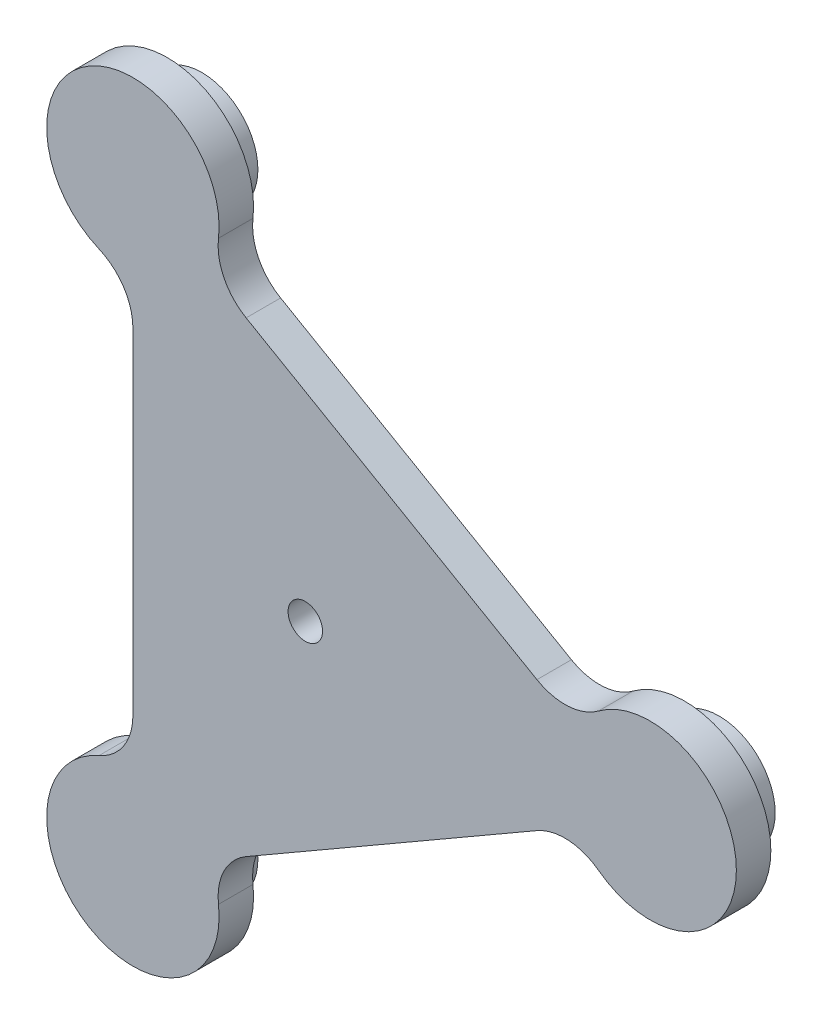
SolidWorks part; units mm, degrees
ref_plane "Front Plane" through (0, 0, 0) normal (0, 0, 1) x (1, 0, 0)
ref_plane "Top Plane" through (0, 0, 0) normal (0, 1, 0) x (1, 0, 0)
ref_plane "Right Plane" through (0, 0, 0) normal (1, 0, 0) x (0, 0, -1)
sketch "Sketch1" plane through (0, 0, 0) normal (0, 0, -1) x (1, 0, 0)
  line L0 (67.1651, 18.9572) -> (-17.1652, 67.6453)
  line L1 (-17.1652, -67.6453) -> (67.1652, -18.9572)
  line L6 (-50, 48.6881) -> (-50, -48.6881)
  arc A1 (-59.8485, -63.6241) -> (-25.1758, -83.6423) centre (-50, -86.6025) ccw
  circle A3 centre (-50, -86.6025) radius 16.25 construction
  arc A4 (-59.8485, -63.6241) -> (-50, -48.6881) centre (-66.25, -48.6881) ccw
  arc A5 (-25.1758, -83.6423) -> (-17.1652, -67.6453) centre (-9.0402, -81.7182) cw
  arc A6 (-25.1759, 83.6423) -> (-59.8485, 63.6241) centre (-50, 86.6025) ccw
  circle A7 centre (-50, 86.6025) radius 16.25 construction
  arc A8 (-25.1759, 83.6423) -> (-17.1652, 67.6453) centre (-9.0402, 81.7182) ccw
  arc A9 (-59.8485, 63.6241) -> (-50, 48.6881) centre (-66.25, 48.6881) cw
  arc A10 (85.0243, -20.0182) -> (85.0243, 20.0183) centre (100, 0) ccw
  circle A11 centre (100, 0) radius 16.25 construction
  arc A12 (85.0243, -20.0182) -> (67.1652, -18.9572) centre (75.2902, -33.0301) ccw
  arc A13 (85.0243, 20.0183) -> (67.1651, 18.9572) centre (75.2901, 33.0301) cw
  point P31 (0, 0)
  dimension "D3" = 50
  dimension "D4" = 32.5
  dimension "D5" = 16.25
  dimension "D6" = 3
extrude "Boss-Extrude1" add sketch "Sketch1" along normal blind 10 contours A10 A13 L0 A8 A6 A9 L6 A4 A1 A5 L1 A12 | A7 | L0 A8 A6 A9 L6 A4 A1 A5 L1 A12 A10 A13 region at (0, 0, 0)
sketch "Sketch2" plane through (0, 0, -10) normal (0, 0, -1) x (1, 0, 0)
  line L9 (67.1651, 18.9572) -> (-17.1652, 67.6453)
  line L10 (-50, 48.6881) -> (-50, -48.6881)
  line L11 (-17.1652, -67.6453) -> (67.1652, -18.9572)
  line L12 (67.1651, 18.9572) -> (-17.1652, 67.6453) construction
  line L13 (-50, 48.6881) -> (-50, -48.6881) construction
  line L14 (-17.1652, -67.6453) -> (67.1652, -18.9572) construction
  circle A6 centre (-50, 86.6025) radius 16.25
  circle A7 centre (100, 0) radius 16.25
  circle A8 centre (-50, -86.6025) radius 16.25
  arc A39 (67.1651, 18.9572) -> (85.0243, 20.0183) centre (75.2901, 33.0301) ccw
  arc A40 (-25.1759, 83.6423) -> (-17.1652, 67.6453) centre (-9.0402, 81.7182) ccw
  arc A41 (-25.1759, 83.6423) -> (-59.8485, 63.6241) centre (-50, 86.6025) ccw
  arc A42 (-50, 48.6881) -> (-59.8485, 63.6241) centre (-66.25, 48.6881) ccw
  arc A43 (-59.8485, -63.6241) -> (-50, -48.6881) centre (-66.25, -48.6881) ccw
  arc A44 (-59.8485, -63.6241) -> (-25.1758, -83.6423) centre (-50, -86.6025) ccw
  arc A45 (-17.1652, -67.6453) -> (-25.1758, -83.6423) centre (-9.0402, -81.7182) ccw
  arc A46 (85.0243, -20.0182) -> (67.1652, -18.9572) centre (75.2902, -33.0301) ccw
  arc A47 (85.0243, -20.0182) -> (85.0243, 20.0183) centre (100, 0) ccw
  arc A48 (67.1651, 18.9572) -> (85.0243, 20.0183) centre (75.2901, 33.0301) ccw construction
  arc A49 (-25.1759, 83.6423) -> (-17.1652, 67.6453) centre (-9.0402, 81.7182) ccw construction
  arc A50 (-25.1759, 83.6423) -> (-59.8485, 63.6241) centre (-50, 86.6025) ccw construction
  arc A51 (-50, 48.6881) -> (-59.8485, 63.6241) centre (-66.25, 48.6881) ccw construction
  arc A52 (-59.8485, -63.6241) -> (-50, -48.6881) centre (-66.25, -48.6881) ccw construction
  arc A53 (-59.8485, -63.6241) -> (-25.1758, -83.6423) centre (-50, -86.6025) ccw construction
  arc A54 (-17.1652, -67.6453) -> (-25.1758, -83.6423) centre (-9.0402, -81.7182) ccw construction
  arc A55 (85.0243, -20.0182) -> (67.1652, -18.9572) centre (75.2902, -33.0301) ccw construction
  arc A56 (85.0243, -20.0182) -> (85.0243, 20.0183) centre (100, 0) ccw construction
  point P27 (0, 0)
  dimension "D2" = 32.5
  dimension "D1" = 0
extrude "Boss-Extrude2" add sketch "Sketch2" along normal blind 10
ref_axis "Axis1" through (0, 0, 0.5) along (0, 0, -1)
ref_plane "Plane1" through (0, 0, 0) normal (0.5, -0.866, 0) x (0, 0, -1)
ref_plane "Plane2" through (0, 0, 0) normal (0.5, 0.866, 0) x (0, 0, -1)
sketch "Sketch3" plane through (0, 0, 0) normal (0, 0, 1) x (1, 0, 0)
  circle A9 centre (0, 0) radius 5
extrude "Cut-Extrude1" cut sketch "Sketch3" against normal blind 10
